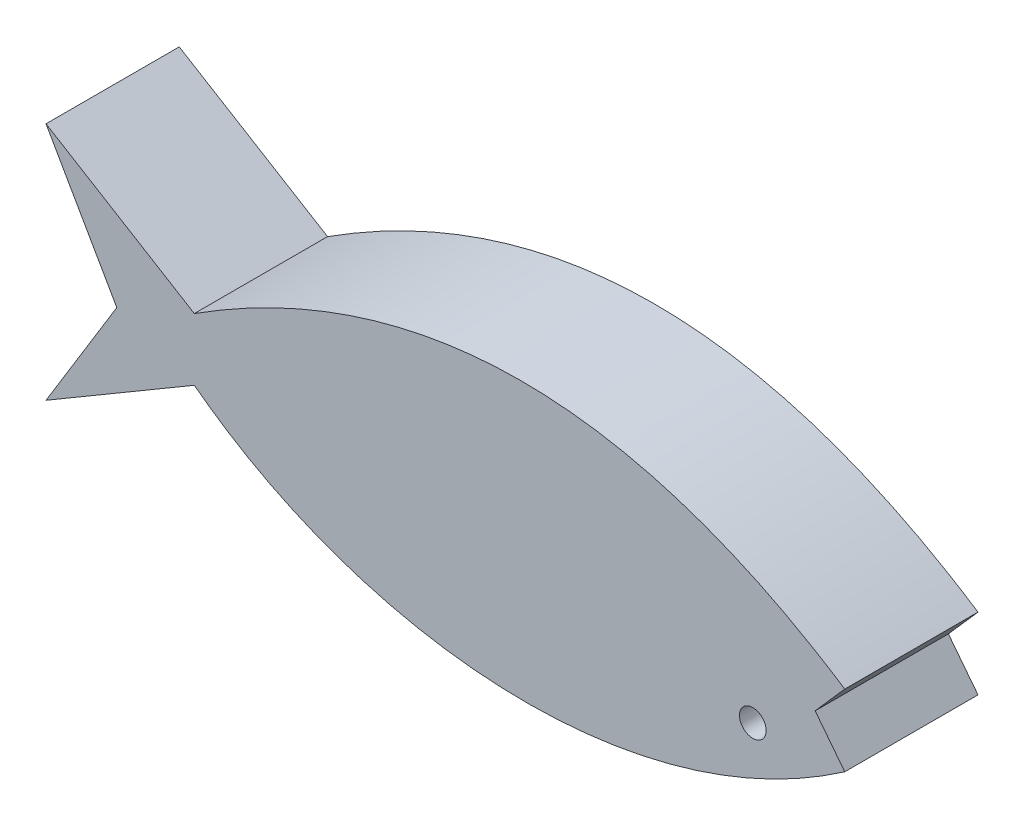
SolidWorks part; units mm, degrees
ref_plane "Front" through (0, 0, 0) normal (0, 0, 1) x (1, 0, 0)
ref_plane "Top" through (0, 0, 0) normal (0, 1, 0) x (1, 0, 0)
ref_plane "Right" through (0, 0, 0) normal (1, 0, 0) x (0, 0, -1)
sketch "Sketch2" plane through (0, 0, 0) normal (0, 0, -1) x (1, 0, 0)
  line L0 (29.973, 6.6427) -> (28.8624, 5.2157)
  line L1 (28.8624, 5.2157) -> (29.973, 3.9538)
  line L2 (5.5653, 6.2857) -> (0, 9.5561)
  line L3 (0, 9.5561) -> (2.6565, 5.2157)
  line L4 (2.6565, 5.2157) -> (0, 0.5701)
  line L5 (0, 0.5701) -> (5.5653, 3.9538)
  circle A0 centre (26.5226, 6.7807) radius 0.5001
  spline S0 degree 3 poles (5.5653, 6.2857) (12.0373, 11.2173) (22.1418, 12.0787) (29.973, 6.6427) knots 0 0 0 0 1 1 1 1
  spline S1 degree 2 poles (5.5653, 3.9538) (17.9191, -3.9397) (29.973, 3.9538) knots 0 0 0 1 1 1
extrude "Boss-Extrude1" add sketch "Sketch2" along normal blind 5
ref_plane "Fish Top Plane" through (0, 0, -5) normal (0, 0, -1) x (1, 0, 0)
sketch "Sketch4" plane through (0, 0, -5) normal (0, 0, -1) x (1, 0, 0)
  line L0 (13.5059, 9.2075) -> (13.5059, 1.4231)
  line L1 (13.5059, 1.4231) -> (15.6022, 1.4231)
  line L2 (15.6022, 1.4231) -> (15.6022, 5.3153)
  line L3 (20.0021, 8.9817) -> (19.8209, 6.4162)
  spline S0 degree 3 poles (13.5059, 9.2075) (15.7232, 8.8861) (17.0355, 7.3523) (18.6802, 4.9177) knots 0 0 0 0 1 1 1 1
  spline S1 degree 3 poles (18.6802, 4.9177) (19.0075, 4.4311) (19.8078, 4.0125) (20.2215, 4.0696) knots 0 0 0 0 1 1 1 1
  spline S2 degree 3 poles (20.2215, 4.0696) (20.6911, 4.1219) (21.1555, 4.4545) (21.1672, 5.1256) knots 0 0 0 0 1 1 1 1
  spline S3 degree 3 poles (21.1672, 5.1256) (21.1805, 6.0722) (20.441, 6.4609) (19.8209, 6.4162) knots 0 0 0 0 1 1 1 1
  spline S4 degree 3 poles (15.6022, 5.3153) (16.5518, 4.7716) (17.8191, 2.3847) (18.2446, 2.1883) knots 0 0 0 0 1 1 1 1
  spline S5 degree 3 poles (18.2446, 2.1883) (18.7799, 1.7004) (19.4638, 1.4548) (20.296, 1.4722) knots 0 0 0 0 1 1 1 1
  spline S6 degree 3 poles (20.296, 1.4722) (21.9479, 1.517) (22.9284, 2.7943) (23.0741, 5.3153) knots 0 0 0 0 1 1 1 1
  spline S7 degree 3 poles (20.0021, 8.9817) (21.932, 8.8417) (22.9793, 7.8879) (23.0741, 5.3153) knots 0 0 0 0 1 1 1 1
extrude "Boss-Extrude2" add sketch "Sketch4" along normal blind 1
